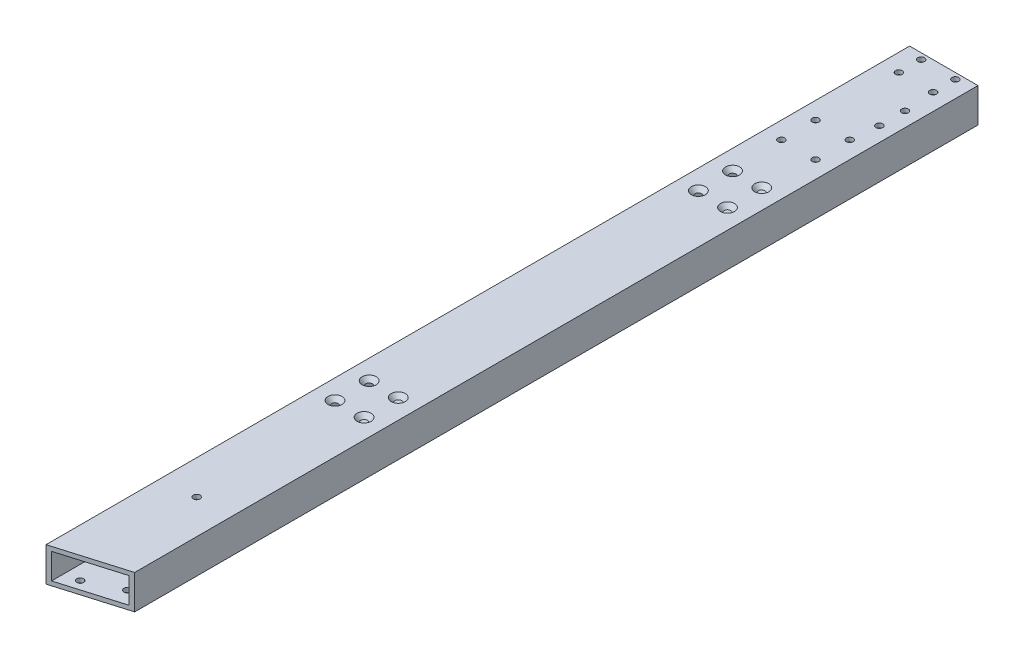
SolidWorks part; units mm, degrees
material "1060 Alloy"
ref_plane "Front Plane" through (0, 0, 0) normal (0, 0, 1) x (1, 0, 0)
ref_plane "Top Plane" through (0, 0, 0) normal (0, 1, 0) x (1, 0, 0)
ref_plane "Right Plane" through (0, 0, 0) normal (1, 0, 0) x (0, 0, -1)
sketch "Sketch1" plane through (0, 0, 0) normal (0, 0, 1) x (1, 0, 0)
  line L0 (-22.225, 9.525) -> (22.225, 9.525)
  line L2 (-25.4, 12.7) -> (25.4, 12.7)
  line L3 (-25.4, 12.7) -> (-25.4, -12.7)
  line L4 (-25.4, -12.7) -> (25.4, -12.7)
  line L5 (25.4, 12.7) -> (25.4, -12.7)
  line L10 (22.225, 9.525) -> (22.225, -9.525)
  line L11 (-22.225, -9.525) -> (22.225, -9.525)
  line L12 (-22.225, 9.525) -> (-22.225, -9.525)
  point P12 (0, 12.7)
  point P14 (25.4, 0)
  dimension "Wall Thickness" = 3.175
  dimension "Outside Width" = 50.8
  dimension "Outside Height" = 25.4
  dimension "Inside Height" = 19.05
  dimension "Inside Width" = 44.45
sketch "Sketch2" plane through (0, 0, 0) normal (1, 0, 0) x (0, 0, -1)
  line L0 (320.675, 0) -> (-320.675, 0)
  point P4 (0, 0)
  point P7 (-320.675, 0)
  point P10 (320.675, 0)
  dimension "Length" = 641.35
sketch "Sketch3" plane through (0, 0, 0) normal (0, 0, 1) x (1, 0, 0)
  line L21 (25.4, 12.7) -> (-25.4, 12.7)
  line L22 (25.4, -12.7) -> (25.4, 12.7)
  line L23 (-25.4, -12.7) -> (25.4, -12.7)
  line L24 (-25.4, 12.7) -> (-25.4, -12.7)
  line L25 (25.4, 12.7) -> (-25.4, 12.7)
  line L26 (25.4, -12.7) -> (25.4, 12.7)
  line L27 (-25.4, -12.7) -> (25.4, -12.7)
  line L28 (-25.4, 12.7) -> (-25.4, -12.7)
  line L29 (22.225, 9.525) -> (-22.225, 9.525)
  line L30 (22.225, -9.525) -> (22.225, 9.525)
  line L31 (-22.225, -9.525) -> (22.225, -9.525)
  line L32 (-22.225, 9.525) -> (-22.225, -9.525)
  line L33 (22.225, 9.525) -> (-22.225, 9.525)
  line L34 (22.225, -9.525) -> (22.225, 9.525)
  line L35 (-22.225, -9.525) -> (22.225, -9.525)
  line L36 (-22.225, 9.525) -> (-22.225, -9.525)
  dimension "D1" = 0
  dimension "D2" = 0
extrude "Boss-Extrude1" add sketch "Sketch3" along normal up to vertex (320.675 mm away) and the other way up to vertex (320.675 mm away) up to point (0, 0, 320.675) other way up to point (0, 0, -320.675)
sketch "Drawing Reference" plane through (0, 0, 0) normal (1, 0, 0) x (0, 0, -1)
  line L0 (-320.675, 0) -> (320.675, 0) construction
  line L1 (0, -12.7) -> (0, 12.7) construction
  line L2 (-320.675, -12.7) -> (320.675, -12.7) construction
  line L5 (-320.675, 12.7) -> (320.675, 12.7) construction
  point P7 (-284.099, 0)
  point P8 (284.099, 0)
  dimension "D1" = 36.576
sketch "Sketch4" plane through (0, 12.7, 0) normal (0, 1, 0) x (1, 0, 0)
  line L0 (-25.4, -320.675) -> (25.4, -305.6274)
  line L1 (25.4, -320.675) -> (25.4, 320.675) construction
  line L2 (25.4, -320.675) -> (-25.4, -320.675)
  dimension "D1" = 16.5
extrude "Cut-Extrude1" cut sketch "Sketch4" against normal through all and the other way through all flip side to cut
sketch "Sketch6" plane through (0, -12.7, 0) normal (0, -1, 0) x (1, 0, 0)
  line L0 (25.4, 305.6274) -> (22.1108, 294.5233) construction
  line L1 (25.4, 279.2824) -> (22.225, 279.2824) construction
  line L2 (25.4, 305.6274) -> (25.4, -320.675) construction
  line L3 (22.225, 279.2824) -> (22.225, 313.1512) construction
  line L4 (22.1108, 294.5233) -> (11.811, 297.5742) construction
  line L5 (-11.811, 250.3501) -> (-11.811, 328.3651) construction
  line L6 (-25.4, 320.675) -> (-27.5213, 313.5136) construction
  line L7 (-25.4, 287.6223) -> (-22.225, 287.6223) construction
  line L8 (-25.4, 320.675) -> (-25.4, -320.675) construction
  line L9 (-22.225, 287.6223) -> (-22.225, 328.3651) construction
  line L10 (-27.5213, 313.5136) -> (-11.811, 308.86) construction
  line L11 (11.811, 250.3501) -> (11.811, 313.1512) construction
  line L12 (-27.5213, 313.5136) -> (-36.5388, 283.071) construction
  line L13 (22.1108, 294.5233) -> (13.0933, 264.0807) construction
  line L14 (-37.6746, 250.3501) -> (48.6057, 250.3501) construction
  line L15 (-11.811, 287.6223) -> (-11.811, 328.3651) construction
  line L16 (11.811, 279.2824) -> (11.811, 313.1512) construction
  line L17 (-36.5388, 283.071) -> (-11.811, 275.7463) construction
  line L18 (13.0933, 264.0807) -> (11.811, 264.4606) construction
  dimension "D1" = 10.414
  dimension "D2" = 10.414
hole_wizard "#10 Clearance Hole1" positions "Sketch7" profile "Sketch8" hole size "#10" standard "ANSI Inch"
sketch "Sketch7" plane through (0, -12.7, 0) normal (0, -1, 0) x (-1, 0, 0)
  point P0 (-11.811, -264.4606)
  point P3 (11.811, -275.7463)
  point P7 (-11.811, -297.5742)
  point P10 (11.811, -308.86)
sketch "Sketch8" plane through (11.811, -12.7, 264.4606) normal (1, 0, 0) x (0, 0, -1)
  line L0 (0, 0) -> (0, 6.5757)
  line L1 (0, 6.5757) -> (2.4892, 5.08)
  line L2 (2.4892, 5.08) -> (2.4892, 0)
  line L5 (2.4892, 0) -> (0, 0)
  line L10 (0, 6.5757) -> (-2.4892, 5.08) construction
  line L11 (0, -6.35) -> (0, 107.95) construction
  dimension "Hole Dia." = 4.9784
  dimension "Hole Depth" = 5.08
  dimension "Drill Angle" = 118
sketch "Sketch9" plane through (0, 12.7, 0) normal (0, 1, 0) x (1, 0, 0)
  line L0 (-12.3709, 316.23) -> (-9.8309, 316.23) construction
  line L2 (-9.1044, 314.5662) -> (-9.0928, 314.5269) construction
  line L3 (10.4891, 316.23) -> (13.0291, 316.23) construction
  line L4 (13.0291, 299.72) -> (10.4891, 299.72) construction
  line L5 (-9.8309, 299.72) -> (-12.3709, 299.72) construction
hole_wizard "#10 Clearance Hole2" positions "Sketch10" profile "Sketch11" hole size "#10" standard "ANSI Inch"
sketch "Sketch10" plane through (0, 12.7, 0) normal (0, 1, 0) x (1, 0, 0)
  point P0 (13.0291, 299.72)
  point P3 (-12.3709, 299.72)
  point P6 (13.0291, 316.23)
  point P9 (-12.3709, 316.23)
sketch "Sketch11" plane through (13.0291, 12.7, -299.72) normal (1, 0, 0) x (0, 0, 1)
  line L0 (0, 0) -> (0, 6.5757)
  line L1 (0, 6.5757) -> (2.4892, 5.08)
  line L2 (2.4892, 5.08) -> (2.4892, 0)
  line L5 (2.4892, 0) -> (0, 0)
  line L10 (0, 6.5757) -> (-2.4892, 5.08) construction
  line L11 (0, -6.35) -> (0, 107.95) construction
  dimension "Hole Dia." = 4.9784
  dimension "Hole Depth" = 5.08
  dimension "Drill Angle" = 118
sketch "Sketch12" plane through (0, 12.7, 0) normal (0, 1, 0) x (1, 0, 0)
  line L0 (-12.7, 238.125) -> (12.7, 238.125) construction
  line L1 (12.7, 238.125) -> (12.7, 212.725) construction
  line L2 (12.7, 212.725) -> (-12.7, 212.725) construction
  line L3 (-12.7, 212.725) -> (-12.7, 238.125) construction
hole_wizard "#10 Clearance Hole3" positions "Sketch13" profile "Sketch14" hole size "#10" standard "ANSI Inch" end condition through all
sketch "Sketch13" plane through (0, 12.7, 0) normal (0, 1, 0) x (1, 0, 0)
  point P0 (-12.7, 212.725)
  point P3 (12.7, 212.725)
  point P6 (12.7, 238.125)
  point P9 (-12.7, 238.125)
  point P12 (14.6226, 277.2519)
  point P15 (14.6226, 258.2019)
sketch "Sketch14" plane through (-12.7, 12.7, -212.725) normal (1, 0, 0) x (0, 0, 1)
  line L0 (0, 0) -> (0, 25.4)
  line L1 (0, 25.4) -> (2.4892, 25.4)
  line L2 (2.4892, 25.4) -> (2.4892, 0)
  line L5 (2.4892, 0) -> (0, 0)
  line L11 (0, -6.35) -> (0, 107.95) construction
  dimension "Thru Hole Dia." = 4.9784
  dimension "Thru Hole Depth" = 25.4
sketch "Sketch17" plane through (0, 12.7, 0) normal (0, 1, 0) x (1, 0, 0)
  point P0 (-0.0762, -234.0972)
hole_wizard "#10 Clearance Hole4" positions "Sketch15" profile "Sketch16" hole size "#10" standard "ANSI Inch" end condition through all
sketch "Sketch15" plane through (0, 12.7, 0) normal (0, 1, 0) x (1, 0, 0)
  point P0 (-0.0762, -234.0972)
sketch "Sketch16" plane through (-0.0762, 12.7, 234.0972) normal (1, 0, 0) x (0, 0, 1)
  line L0 (0, 0) -> (0, 25.4)
  line L1 (0, 25.4) -> (2.4892, 25.4)
  line L2 (2.4892, 25.4) -> (2.4892, 0)
  line L5 (2.4892, 0) -> (0, 0)
  line L11 (0, -6.35) -> (0, 107.95) construction
  dimension "Thru Hole Dia." = 4.9784
  dimension "Thru Hole Depth" = 25.4
hole_wizard "Tap Drill for #10-32 Tap1" positions "Sketch18" profile "Sketch19" hole size "#10-32" standard "ANSI Inch" end condition through all
sketch "Sketch18" plane through (0, -12.7, 0) normal (0, -1, 0) x (-1, 0, 0)
  point P0 (-10.8204, -95.25)
  point P3 (-10.8204, -120.65)
  point P6 (10.8204, -120.65)
  point P9 (10.8204, -95.25)
  point P12 (10.8204, 174.625)
  point P15 (-10.8204, 174.625)
  point P18 (-10.8204, 149.225)
  point P21 (10.8204, 149.225)
sketch "Sketch19" plane through (10.8204, -12.7, 95.25) normal (1, 0, 0) x (0, 0, -1)
  line L0 (0, 0) -> (0, 25.4)
  line L1 (0, 25.4) -> (5.2197, 25.4)
  line L2 (2.0193, 21.7184) -> (2.0193, 0)
  line L5 (2.0193, 0) -> (0, 0)
  line L7 (5.2197, 25.4) -> (2.0193, 21.7184)
  line L8 (-5.2197, 25.4) -> (-2.0193, 21.7184) construction
  line L11 (0, -6.35) -> (0, 107.95) construction
  dimension "Thru Hole Dia." = 4.0386
  dimension "Thru Hole Depth" = 25.4
  dimension "Far C'Sink Dia." = 10.4394
  dimension "Far C'Sink Angle" = 82
equation "\"D1@Drawing Reference\"=\"Outside Width@Sketch1\" * 0.72"
